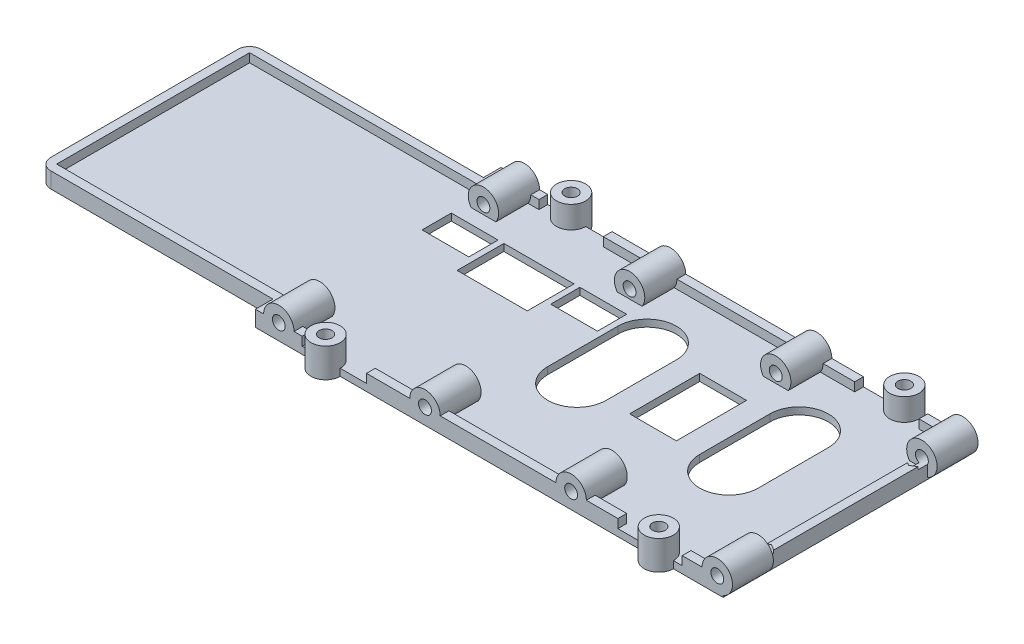
SolidWorks part; units mm, degrees
ref_plane "Front Plane" through (0, 0, 0) normal (0, 0, 1) x (1, 0, 0)
ref_plane "Top Plane" through (0, 0, 0) normal (0, 1, 0) x (1, 0, 0)
ref_plane "Right Plane" through (0, 0, 0) normal (1, 0, 0) x (0, 0, -1)
sketch "Sketch1" plane through (0, 0, 0) normal (0, 1, 0) x (1, 0, 0)
  line L1 (-30, 10.5) -> (30, 10.5)
  line L2 (-30, 10.5) -> (-30, -10.5)
  line L3 (-30, -10.5) -> (30, -10.5)
  line L4 (30, 10.5) -> (30, -10.5)
  line L5 (-30, 10.5) -> (30, -10.5) construction
  line L6 (-30, -10.5) -> (30, 10.5) construction
  point P0 (0, 0)
  dimension "D1" = 21
  dimension "D2" = 60
extrude "Boss-Extrude1" add sketch "Sketch1" along normal blind 1.35
sketch "Sketch2" plane through (0, 1.35, 0) normal (0, 1, 0) x (1, 0, 0)
  line L0 (21.5, 4.5) -> (21.5, -1.5) construction
  line L1 (24, 4.5) -> (24, -1.5)
  line L2 (19, 4.5) -> (19, -1.5)
  line L3 (8.5, 4.5) -> (8.5, -1.5) construction
  line L4 (11, 4.5) -> (11, -1.5)
  line L5 (6, 4.5) -> (6, -1.5)
  line L7 (13, 4.5) -> (17, 4.5)
  line L8 (13, 4.5) -> (13, -1.5)
  line L9 (13, -1.5) -> (17, -1.5)
  line L10 (17, 4.5) -> (17, -1.5)
  line L11 (1.5, 5.75) -> (5.5, 5.75)
  line L12 (1.5, 5.75) -> (1.5, 3.25)
  line L13 (1.5, 3.25) -> (5.5, 3.25)
  line L14 (5.5, 5.75) -> (5.5, 3.25)
  line L15 (1.5, 5.75) -> (5.5, 3.25) construction
  line L16 (1.5, 3.25) -> (5.5, 5.75) construction
  line L17 (-5, 5.75) -> (1, 5.75)
  line L18 (-5, 5.75) -> (-5, 1.75)
  line L19 (-5, 1.75) -> (1, 1.75)
  line L20 (1, 5.75) -> (1, 1.75)
  line L21 (-5, 5.75) -> (1, 1.75) construction
  line L22 (-5, 1.75) -> (1, 5.75) construction
  line L23 (-9.5, 5.75) -> (-5.5, 5.75)
  line L24 (-9.5, 5.75) -> (-9.5, 3.25)
  line L25 (-9.5, 3.25) -> (-5.5, 3.25)
  line L26 (-5.5, 5.75) -> (-5.5, 3.25)
  line L27 (-9.5, 5.75) -> (-5.5, 3.25) construction
  line L28 (-9.5, 3.25) -> (-5.5, 5.75) construction
  line L29 (-30, 10.5) -> (-10, 10.5)
  line L30 (-30, 10.5) -> (-30, 9)
  line L31 (-30, 9) -> (-10, 9)
  line L32 (-10, 10.5) -> (-10, 9)
  line L35 (-30, -10.5) -> (-10, -10.5)
  line L36 (-30, -10.5) -> (-30, -9)
  line L37 (-30, -9) -> (-10, -9)
  line L38 (-10, -10.5) -> (-10, -9)
  arc A0 (24, 4.5) -> (19, 4.5) centre (21.5, 4.5) ccw
  arc A1 (19, -1.5) -> (24, -1.5) centre (21.5, -1.5) ccw
  arc A2 (11, 4.5) -> (6, 4.5) centre (8.5, 4.5) ccw
  arc A3 (6, -1.5) -> (11, -1.5) centre (8.5, -1.5) ccw
  point P2 (21.5, 1.5)
  point P7 (8.5, 1.5)
  point P18 (3.5, 4.5)
  point P23 (-2, 3.75)
  point P28 (-7.5, 4.5)
  line M36 (-30, 10.5) -> (-30, -10.5)
  line M37 (-30, -10.5) -> (30, -10.5)
  dimension "D1" = 20
  dimension "D2" = 1.5
extrude "Cut-Extrude1" cut sketch "Sketch2" against normal through all contours L38 L37 M37 M36 | L26 L23 L24 L25 | L20 L17 L18 L19 | L14 L11 L12 L13 | L5 A3 L4 A2 | L10 L7 L8 L9 | L2 A1 L1 A0 | L31 L32 L29 L30 region at (21.5, 1.35, -1.5) region at (8.5, 1.35, -1.5) region at (15, 1.35, -1.5) region at (3.5, 1.35, -4.5) region at (-2, 1.35, -3.75) region at (-7.5, 1.35, -4.5) region at (-20, 1.35, 9.75)
sketch "Sketch3" plane through (0, 1.35, 0) normal (0, 1, 0) x (1, 0, 0)
  line L8 (30, 10.5) -> (-10, 10.5) construction
  line L9 (-6, 10.5) -> (-0.5, 10.5)
  line L10 (-6, 10.5) -> (-6, -10.5)
  line L11 (-6, -10.5) -> (-0.5, -10.5)
  line L12 (-0.5, 10.5) -> (-0.5, -10.5)
  line L13 (-10, -10.5) -> (30, -10.5) construction
  line L14 (30, -10.5) -> (30, 10.5) construction
  line L15 (21, 10.5) -> (26.5, 10.5)
  line L16 (-29.25, 8.25) -> (-29.25, -8.25)
  line L17 (-29.25, -8.25) -> (-9.25, -8.25)
  line L18 (-9.25, -8.25) -> (-9.25, -9.75)
  line L19 (-9.25, -9.75) -> (29.25, -9.75)
  line L20 (29.25, -9.75) -> (29.25, 9.75)
  line L21 (29.25, 9.75) -> (-9.25, 9.75)
  line L22 (-9.25, 9.75) -> (-9.25, 8.25)
  line L23 (-9.25, 8.25) -> (-29.25, 8.25)
  line L24 (-29.25, 8.25) -> (-29.25, -8.25)
  line L25 (-29.25, -8.25) -> (-9.25, -8.25)
  line L26 (-9.25, -8.25) -> (-9.25, -9.75)
  line L27 (-9.25, -9.75) -> (29.25, -9.75)
  line L28 (29.25, -9.75) -> (29.25, 9.75)
  line L29 (29.25, 9.75) -> (-9.25, 9.75)
  line L30 (-9.25, 9.75) -> (-9.25, 8.25)
  line L31 (-9.25, 8.25) -> (-29.25, 8.25)
  line L32 (21, 10.5) -> (21, -10.5)
  line L33 (21, -10.5) -> (26.5, -10.5)
  line L34 (26.5, 10.5) -> (26.5, -10.5)
  arc M9 (19, 4.5) -> (24, 4.5) centre (21.5, 4.5) cw
  line M10 (24, 4.5) -> (24, -1.5)
  arc M11 (24, -1.5) -> (19, -1.5) centre (21.5, -1.5) cw
  line M12 (19, -1.5) -> (19, 4.5)
  arc M13 (6, 4.5) -> (11, 4.5) centre (8.5, 4.5) cw
  line M14 (11, 4.5) -> (11, -1.5)
  arc M15 (11, -1.5) -> (6, -1.5) centre (8.5, -1.5) cw
  line M16 (6, -1.5) -> (6, 4.5)
  line M17 (13, -1.5) -> (13, 4.5)
  line M18 (13, 4.5) -> (17, 4.5)
  line M19 (17, 4.5) -> (17, -1.5)
  line M20 (17, -1.5) -> (13, -1.5)
  line M21 (5.5, 5.75) -> (5.5, 3.25)
  line M22 (5.5, 3.25) -> (1.5, 3.25)
  line M23 (1.5, 3.25) -> (1.5, 5.75)
  line M24 (1.5, 5.75) -> (5.5, 5.75)
  line M25 (1, 5.75) -> (1, 1.75)
  line M26 (1, 1.75) -> (-5, 1.75)
  line M27 (-5, 1.75) -> (-5, 5.75)
  line M28 (-5, 5.75) -> (1, 5.75)
  line M29 (-5.5, 5.75) -> (-5.5, 3.25)
  line M30 (-5.5, 3.25) -> (-9.5, 3.25)
  line M31 (-9.5, 3.25) -> (-9.5, 5.75)
  line M32 (-9.5, 5.75) -> (-5.5, 5.75)
  line M38 (-10, -10.5) -> (30, -10.5)
  line M40 (30, 10.5) -> (-10, 10.5)
  dimension "D2" = 5.5
  dimension "D3" = 4
  dimension "D4" = 5.5
  dimension "D5" = 3.5
  dimension "D1" = 0.75
extrude "Cut-Extrude2" cut sketch "Sketch3" against normal blind 0.75 contours L30 L31 L24 L25 L26 L27 L10 L29 M30 M31 M32 | L32 L29 L12 L27 M28 M25 M26 M11 M12 M9 M17 M18 M19 M20 M23 M24 M21 M22 M15 M16 M13 M14 | L12 L29 L10 L27 M32 M29 M30 M26 M27 M28 | L34 L29 L32 L27 M9 M10 M11 | L29 L34 L27 L28 | L27 L10 L12 M38 | L29 L12 L10 M40 | L34 L27 L32 M38 | L34 L32 L29 M40 region at (-3.25, 1.35, -10.125) region at (-3.3168, 1.35, 0.831) region at (-17.5962, 1.35, 0.1024) region at (10.25, 1.35, -9.4597) region at (23.75, 1.35, -10.125) region at (24.2747, 1.35, 0.5907) region at (27.875, 1.35, 0) region at (-3.25, 1.35, 10.125) region at (23.75, 1.35, 10.125)
sketch "Sketch5" plane through (0, 0, 10.5) normal (0, 0, 1) x (1, 0, 0)
  line L0 (-10, 1.35) -> (-6, 1.35) construction
  circle A0 centre (-8, 1.35) radius 1.3
  dimension "D1" = 2.6
extrude "Boss-Extrude2" add sketch "Sketch5" against normal blind 3.5
pattern_linear "LPattern1" count 4 spacing 12.5 along (1, 0, 0) of "Boss-Extrude2"
sketch "Sketch6" plane through (0, 0, 0) normal (0, -1, 0) x (1, 0, 0)
  line L0 (-10, 10.5) -> (30, 10.5) construction
  line L1 (30, 10.5) -> (30, -10.5) construction
  circle A0 centre (-4, 10.5) radius 1.25
  circle A1 centre (24.5, 10.5) radius 1.25
  dimension "D1" = 2.5
  dimension "D2" = 2.5
  dimension "D3" = 5.5
  dimension "D4" = 28.5
extrude "Boss-Extrude3" add sketch "Sketch6" against normal blind 2.5
hole_wizard "M1.4x0.3 Tapped Hole1" positions "3DSketch1" profile "Sketch7" tap size "M1.4x0.3" standard "ANSI Metric"
sketch3d "3DSketch1"
  line L0 (-8, 1.35, 8.25) -> (-8, 1.35, 10.5) construction
  line L1 (4.5, 1.35, 9.75) -> (4.5, 1.35, 10.5) construction
  line L2 (17, 1.35, 9.75) -> (17, 1.35, 10.5) construction
  line L3 (29.5, 1.35, 7) -> (29.5, 1.35, 9.75) construction
  point P0 (-8, 1.35, 10.5)
  point P4 (4.5, 1.35, 10.5)
  point P8 (17, 1.35, 10.5)
  point P12 (29.5, 1.35, 10.5)
cosmetic thread "Hole Thread1" parameters "D1"=2.8, "D2"=1.4
cosmetic thread "Hole Thread2" parameters "D1"=2.8, "D2"=1.4
cosmetic thread "Hole Thread3" parameters "D1"=2.8, "D2"=1.4
cosmetic thread "Hole Thread4" parameters "D1"=2.8, "D2"=1.4
sketch "Sketch7" plane through (-8, 1.35, 10.5) normal (1, 0, 0) x (0, -1, 0)
  line L0 (0, 0) -> (0, 4.6305)
  line L1 (0, 4.6305) -> (0.55, 4.3)
  line L2 (0.55, 4.3) -> (0.55, 0)
  line L5 (0.55, 0) -> (0, 0)
  line L10 (0, 4.6305) -> (-0.55, 4.3) construction
  line L11 (0, -6.35) -> (0, 107.95) construction
  dimension "Tap Drill Dia." = 1.1
  dimension "Tap Drill Depth" = 4.3
  dimension "Drill Angle" = 118
hole_wizard "M1.4x0.3 Tapped Hole2" positions "3DSketch2" profile "Sketch8" tap size "M1.4x0.3" standard "ANSI Metric"
sketch3d "3DSketch2"
  line L0 (-4, 2.5, 10.5) -> (-4, 0.6, 10.5) construction
  line L1 (24.5, 2.5, 10.5) -> (24.5, 0.6, 10.5) construction
  point P2 (-4, 2.5, 10.5)
  point P11 (24.5, 2.5, 10.5)
sketch "Sketch8" plane through (-4, 2.5, 10.5) normal (1, 0, 0) x (0, 0, 1)
  line L0 (0, 0) -> (0, 4.6305)
  line L1 (0, 4.6305) -> (0.55, 4.3)
  line L2 (0.55, 4.3) -> (0.55, 0)
  line L5 (0.55, 0) -> (0, 0)
  line L10 (0, 4.6305) -> (-0.55, 4.3) construction
  line L11 (0, -6.35) -> (0, 107.95) construction
  dimension "Tap Drill Dia." = 1.1
  dimension "Tap Drill Depth" = 4.3
  dimension "Drill Angle" = 118
cosmetic thread "Hole Thread5" parameters "D1"=2.8, "D2"=1.4
cosmetic thread "Hole Thread13" parameters "D1"=2.8, "D2"=1.4
mirror "Mirror1" about plane through (0, 0, 0) normal (0, 0, 1) of "M1.4x0.3 Tapped Hole2", "M1.4x0.3 Tapped Hole1", "Boss-Extrude3", "LPattern1", "Boss-Extrude2"
cosmetic thread "Hole Thread7" parameters "D1"=2.8, "D2"=1.4
cosmetic thread "Hole Thread9" parameters "D1"=2.8, "D2"=1.4
cosmetic thread "Hole Thread10" parameters "D1"=2.8, "D2"=1.4
cosmetic thread "Hole Thread11" parameters "D1"=2.8, "D2"=1.4
cosmetic thread "Hole Thread12" parameters "D1"=2.8, "D2"=1.4
cosmetic thread "Hole Thread14" parameters "D1"=2.8, "D2"=1.4
fillet "Fillet1" radius 1 2 edges at (-30, 0.675, -9) (-30, 0.675, 9)
